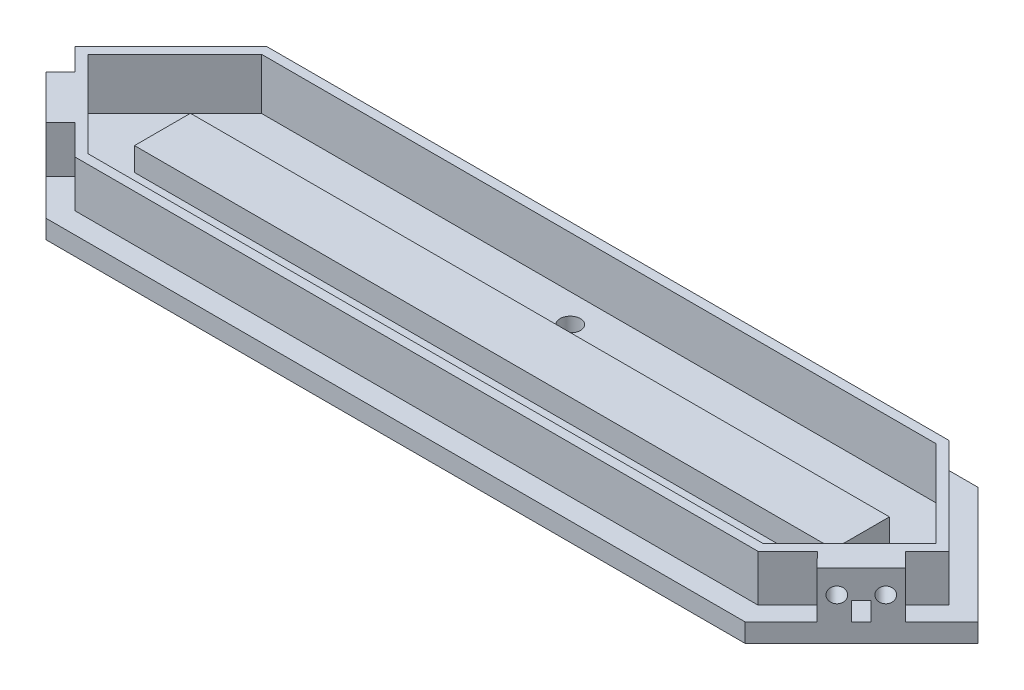
SolidWorks part; units mm, degrees
ref_plane "Ebene vorne" through (0, 0, 0) normal (0, 0, 1) x (1, 0, 0)
ref_plane "Ebene oben" through (0, 0, 0) normal (0, 1, 0) x (1, 0, 0)
ref_plane "Ebene rechts" through (0, 0, 0) normal (1, 0, 0) x (0, 0, -1)
sketch "Skizze1" plane through (0, 0, 0) normal (0, 1, 0) x (1, 0, 0)
  line L1 (-100, -25) -> (100, -25)
  line L2 (-100, -25) -> (-100, 25)
  line L3 (-100, 25) -> (100, 25)
  line L4 (100, -25) -> (100, 25)
  line L5 (-100, -25) -> (100, 25) construction
  line L6 (-100, 25) -> (100, -25) construction
  point P0 (0, 0)
  dimension "D1" = 200
  dimension "D2" = 50
extrude "Aufsatz-Linear austragen1" add sketch "Skizze1" along normal blind 3
chamfer "Fase1" distance 25 angle 45 4 edges at (-100, 1.5, -25) (-100, 1.5, 25) (100, 1.5, -25) (100, 1.5, 25)
sketch "Skizze2" plane through (0, 3, 0) normal (0, 1, 0) x (1, 0, 0)
  line L0 (73.1775, 20.6) -> (93.7775, 0)
  line L1 (93.7775, 0) -> (73.2775, -20.5)
  line L2 (100, 0) -> (75, 25) construction
  line L3 (73.2775, -20.5) -> (-73.2775, -20.5)
  line L4 (-73.1775, 20.6) -> (-93.7775, 0)
  line L5 (-75, 25) -> (-100, 0) construction
  line L6 (-73.1775, 20.6) -> (73.1775, 20.6)
  line L7 (75, 25) -> (-75, 25) construction
  line L8 (75, -25) -> (100, 0) construction
  line L9 (-75, -25) -> (75, -25) construction
  line L10 (-93.7775, 0) -> (-73.2775, -20.5)
  line L11 (-100, 0) -> (-75, -25) construction
  line L12 (-72.349, 18.6) -> (-90.949, 0)
  line L13 (-90.949, 0) -> (-72.449, -18.5)
  line L14 (-72.449, -18.5) -> (72.449, -18.5)
  line L15 (-72.349, 18.6) -> (72.349, 18.6)
  line L16 (72.449, -18.5) -> (90.949, 0)
  line L17 (90.949, 0) -> (72.349, 18.6)
  dimension "D1" = 4.4
  dimension "D2" = 4.4
  dimension "D3" = 4.4
  dimension "D4" = 4.4
  dimension "D5" = 4.4
  dimension "D6" = 4.4
  dimension "D7" = 4.4
  dimension "D8" = 4.5
  dimension "D9" = 4.4
  dimension "D10" = 4.4
  dimension "D11" = 4.4
  dimension "D12" = 2
  dimension "D13" = 2
  dimension "D14" = 2
  dimension "D15" = 2
  dimension "D16" = 2
  dimension "D17" = 2
  dimension "D18" = 2
  dimension "D19" = 2
  dimension "D20" = 2
extrude "Aufsatz-Linear austragen2" add sketch "Skizze2" along normal blind 11 contours L4 L10 L3 L1 L0 L6 L17 L16 L14 L13 L12 L15 region at (82.1198, 3, -8.9423)
sketch "Skizze3" plane through (-46.8887, 0, 46.8887) normal (-0.7071, 0, 0.7071) x (0.7071, 0, 0.7071)
  line L0 (-66.3107, 3) -> (-37.3193, 3) construction
  line L1 (-60.7107, 3) -> (-45.3553, 3)
  line L2 (-60.7107, 3) -> (-60.7107, 14)
  line L3 (-60.7107, 14) -> (-45.3553, 14)
  line L4 (-45.3553, 3) -> (-45.3553, 14)
  line L5 (-66.3107, 14) -> (-37.3193, 14) construction
  dimension "D1" = 10
  dimension "D2" = 10
extrude "Schnitt-Linear austragen1" cut sketch "Skizze3" against normal blind 10
sketch "Skizze4" plane through (46.8887, 0, 46.8887) normal (0.7071, 0, 0.7071) x (0.7071, 0, -0.7071)
  line L0 (66.3107, 3) -> (37.3193, 3) construction
  line L1 (45.3553, 3) -> (60.7107, 3)
  line L2 (45.3553, 3) -> (45.3553, 14)
  line L3 (45.3553, 14) -> (60.7107, 14)
  line L4 (60.7107, 3) -> (60.7107, 14)
  line L5 (66.3107, 14) -> (37.3193, 14) construction
  line L6 (35.3553, 0) -> (35.3553, 3) construction
  line L7 (70.7107, 3) -> (70.7107, 0) construction
  dimension "D1" = 10
  dimension "D2" = 10
extrude "Schnitt-Linear austragen2" cut sketch "Skizze4" against normal blind 10
sketch "Skizze5" plane through (0, 3, 0) normal (0, 1, 0) x (1, 0, 0)
  line L1 (-75.0065, 6) -> (74.9935, 6)
  line L2 (-75.0065, 6) -> (-75.0065, -6)
  line L3 (-75.0065, -6) -> (74.9935, -6)
  line L4 (74.9935, 6) -> (74.9935, -6)
  dimension "D1" = 12
  dimension "D2" = 150
  dimension "D3" = 19
extrude "Aufsatz-Linear austragen3" add sketch "Skizze5" along normal blind 5
sketch "Skizze6" plane through (0, 3, 0) normal (0, 1, 0) x (1, 0, 0)
  line L4 (87.6963, -3.2527) -> (78.2527, -12.6963)
  line L9 (88.4034, -2.5456) -> (89.8177, -3.9598) construction
  line L10 (87.6963, -3.2527) -> (92.2218, -7.7782)
  line L11 (78.2527, -12.6963) -> (82.7351, -17.2649)
  line L12 (92.2218, -7.7782) -> (82.7351, -17.2649)
  line L14 (88.4034, -2.5456) -> (90.949, 0) construction
  line L15 (75, -25) -> (100, 0) construction
  dimension "D1" = 1
  dimension "D2" = 1
  dimension "D3" = 0
  dimension "D4" = 0
  dimension "D5" = 0
extrude "Aufsatz-Linear austragen4" add sketch "Skizze6" along normal blind 11
sketch "Skizze8" plane through (50, 0, 50) normal (0.7071, 0, 0.7071) x (0.7071, 0, -0.7071)
  line L0 (46.2944, 14) -> (46.2944, 3) construction
  line L1 (59.7107, 14) -> (59.7107, 3) construction
  line L3 (51.4944, 4) -> (54.5107, 4)
  line L4 (51.4944, 4) -> (51.4944, 8)
  line L5 (51.4944, 8) -> (54.5107, 8)
  line L6 (54.5107, 4) -> (54.5107, 8)
  line L7 (46.2944, 14) -> (59.7107, 14) construction
  circle A0 centre (49.2944, 9) radius 1.65
  circle A1 centre (56.7107, 9) radius 1.65
  dimension "D1" = 3.3
  dimension "D2" = 3.3
  dimension "D5" = 5
  dimension "D3" = 3
  dimension "D4" = 3
  dimension "D6" = 2.2
  dimension "D7" = 2.2
  dimension "D8" = 5
sketch "Skizze10" plane through (0, 3, 0) normal (0, 1, 0) x (1, 0, 0)
  line L0 (-87.6963, -3.2527) -> (-78.2527, -12.6963)
  line L1 (-87.6963, -3.2527) -> (-92.2218, -7.7782)
  line L2 (-78.2527, -12.6963) -> (-82.7782, -17.2218)
  line L3 (-92.2218, -7.7782) -> (-82.7782, -17.2218)
  line L4 (-88.4034, -2.5456) -> (-89.8177, -3.9598) construction
  line L6 (-77.5456, -13.4034) -> (-78.9598, -14.8177) construction
  line L7 (-77.5456, -13.4034) -> (-72.449, -18.5) construction
  line L8 (-100, 0) -> (-75, -25) construction
  dimension "D1" = 1
  dimension "D2" = 1
  dimension "D3" = 0
  dimension "D4" = 0
  dimension "D5" = 0
  dimension "D6" = 1
  dimension "D7" = 1
extrude "Aufsatz-Linear austragen5" add sketch "Skizze10" along normal blind 11
sketch "Skizze12" plane through (0, 3, 0) normal (0, 1, 0) x (1, 0, 0)
  circle A0 centre (0, 12.5) radius 2.2
  circle A1 centre (0, -12.5) radius 2.2
  dimension "D3" = 4.4
  dimension "D4" = 4.4
  dimension "D1" = 12.5
  dimension "D2" = 12.5
extrude "Schnitt-Linear austragen8" cut sketch "Skizze12" against normal blind 10
sketch "Skizze13" plane through (0, 3, 0) normal (0, 1, 0) x (1, 0, 0)
  line L28 (89.8177, -3.9598) -> (88.4034, -2.5456)
  line L29 (89.8177, -3.9598) -> (89.1071, -4.6704)
  line L30 (88.4034, -2.5456) -> (87.6929, -3.2562)
  line L31 (89.1071, -4.6704) -> (87.6929, -3.2562)
  line L40 (-89.8177, -3.9598) -> (-88.4034, -2.5456)
  line L41 (-89.8177, -3.9598) -> (-89.1038, -4.6737)
  line L42 (-88.4034, -2.5456) -> (-87.6896, -3.2595)
  line L43 (-89.1038, -4.6737) -> (-87.6896, -3.2595)
  line L44 (78.9598, -14.8177) -> (77.5456, -13.4034)
  line L45 (78.9598, -14.8177) -> (79.6713, -14.1061)
  line L46 (77.5456, -13.4034) -> (78.2571, -12.6919)
  line L47 (79.6713, -14.1061) -> (78.2571, -12.6919)
  line L48 (-78.9598, -14.8177) -> (-77.5456, -13.4034)
  line L49 (-78.9598, -14.8177) -> (-79.6764, -14.101)
  line L50 (-77.5456, -13.4034) -> (-78.2622, -12.6868)
  line L51 (-79.6764, -14.101) -> (-78.2622, -12.6868)
extrude "Aufsatz-Linear austragen6" add sketch "Skizze13" along normal blind 11
extrude "Schnitt-Linear austragen9" cut sketch "Skizze8" against normal blind 10
sketch "Skizze14" plane through (0, 3, 0) normal (0, 1, 0) x (1, 0, 0)
  line L0 (-89.1106, -4.6669) -> (-93.7775, 0)
  line L1 (-93.7775, 0) -> (-73.1775, 20.6)
  line L2 (-73.1775, 20.6) -> (73.1775, 20.6)
  line L3 (73.1775, 20.6) -> (93.7775, 0)
  line L4 (93.7775, 0) -> (89.1106, -4.6669)
  line L5 (89.1106, -4.6669) -> (92.2218, -7.7782)
  line L6 (92.2218, -7.7782) -> (100, 0)
  line L7 (100, 0) -> (75, 25)
  line L8 (75, 25) -> (-75, 25)
  line L9 (-75, 25) -> (-100, 0)
  line L10 (-100, 0) -> (-92.2218, -7.7782)
  line L11 (-92.2218, -7.7782) -> (-89.1106, -4.6669)
  line L12 (-82.7782, -17.2218) -> (-79.6669, -14.1106)
  line L13 (-79.6669, -14.1106) -> (-73.2775, -20.5)
  line L14 (-73.2775, -20.5) -> (73.2775, -20.5)
  line L15 (73.2775, -20.5) -> (79.6534, -14.124)
  line L16 (79.6534, -14.124) -> (82.7351, -17.2649)
  line L17 (82.7351, -17.2649) -> (75, -25)
  line L18 (75, -25) -> (-75, -25)
  line L19 (-75, -25) -> (-82.7782, -17.2218)
extrude "Aufsatz-Linear austragen7" add sketch "Skizze14" along normal blind 1
sketch "Skizze11" plane through (-50, 0, 50) normal (-0.7071, 0, 0.7071) x (0.7071, 0, 0.7071)
  line L0 (-46.3553, 14) -> (-46.3553, 4) construction
  line L1 (-59.7107, 14) -> (-59.7107, 4) construction
  line L2 (-59.7107, 14) -> (-46.3553, 14) construction
  line L4 (-54.5107, 4) -> (-51.5553, 4)
  line L5 (-54.5107, 4) -> (-54.5107, 8)
  line L6 (-54.5107, 8) -> (-51.5553, 8)
  line L7 (-51.5553, 4) -> (-51.5553, 8)
  circle A0 centre (-56.7107, 9) radius 1.65
  circle A1 centre (-49.3553, 9) radius 1.65
  dimension "D5" = 3.3
  dimension "D6" = 3.3
  dimension "D1" = 3
  dimension "D2" = 3
  dimension "D3" = 5
  dimension "D4" = 5
  dimension "D7" = 4
  dimension "D8" = 2.2
  dimension "D9" = 2.2
extrude "Schnitt-Linear austragen7" cut sketch "Skizze11" against normal blind 10
